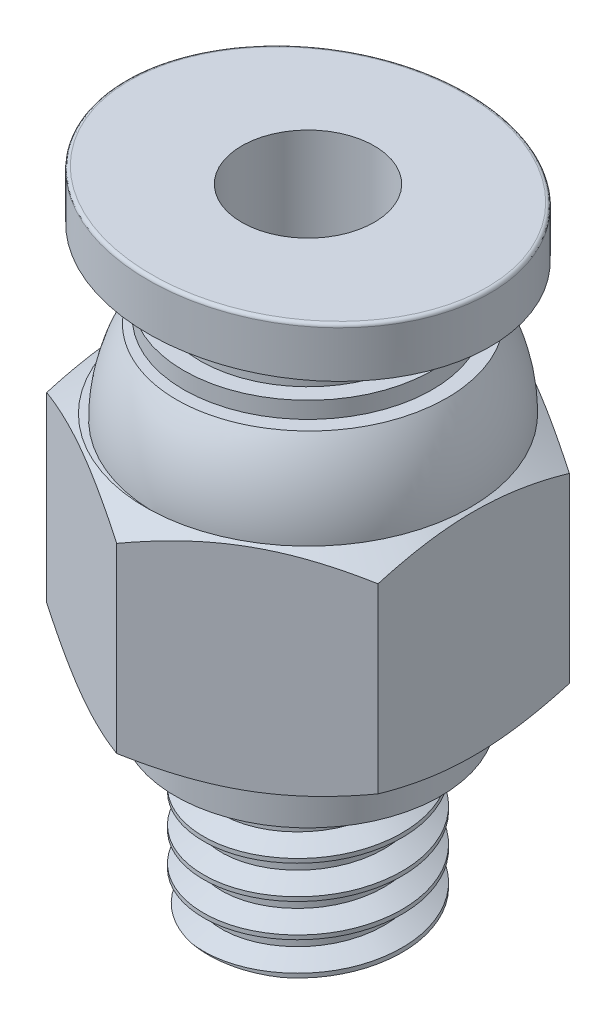
SolidWorks part; units mm, degrees
ref_plane "Спереди" through (0, 0, 0) normal (0, 0, 1) x (1, 0, 0)
ref_plane "Сверху" through (0, 0, 0) normal (0, 1, 0) x (1, 0, 0)
ref_plane "Справа" through (0, 0, 0) normal (1, 0, 0) x (0, 0, -1)
sketch "Эскиз1" plane through (0, 0, 0) normal (0, 1, 0) x (1, 0, 0)
  line L1 (0, 5.7735) -> (-5, 2.8868)
  line L2 (-5, 2.8868) -> (-5, -2.8868)
  line L3 (-5, -2.8868) -> (0, -5.7735)
  line L4 (0, -5.7735) -> (5, -2.8868)
  line L5 (5, -2.8868) -> (5, 2.8868)
  line L6 (5, 2.8868) -> (0, 5.7735)
  circle A0 centre (0, 0) radius 5 construction
  dimension "D1" = 10
extrude "Бобышка-Вытянуть1" add sketch "Эскиз1" along normal mid plane 6.5
sketch "Эскиз4" plane through (0, 0, 0) normal (1, 0, 0) x (0, 0, -1)
  line L0 (-7.1234, 0) -> (0, 0) construction
  line L1 (-4.9, 3.25) -> (-6.9, 2.0953)
  line L2 (-5.7735, 3.25) -> (-2.8868, 3.25) construction
  line L3 (-6.9, 2.0953) -> (-6.9, 3.25)
  line L4 (-6.9, 3.25) -> (-4.9, 3.25)
  line L6 (-6.9, -2.0953) -> (-6.9, -3.25)
  line L7 (-4.9, -3.25) -> (-6.9, -2.0953)
  line L8 (-6.9, -3.25) -> (-4.9, -3.25)
  line L9 (0, 0) -> (0, 4.4661) construction
  dimension "D1" = 2
  dimension "D2" = 4.9
  dimension "D3" = 30
revolve "Вырез-Повернуть1" cut sketch "Эскиз4" angle 360 about L9
sketch "Эскиз5" plane through (0, 3.25, 0) normal (0, 1, 0) x (1, 0, 0)
  line L0 (0.1542, -4.8976) -> (0.1542, 4.8976) construction
  circle A1 centre (0, 0) radius 4.9
  circle A2 centre (0, 0) radius 4.9
  dimension "D1" = 0
revolve "Повернуть2" add sketch "Эскиз5" angle 360 about L0 region at (2.1632, 3.25, 0)
extrude "Вырез-Вытянуть1" cut sketch "Эскиз5<4>" along normal through all from offset 2.5
sketch "Эскиз5<4>" plane through (0, 3.25, 0) normal (0, 1, 0) x (1, 0, 0) same geometry as "Эскиз5"
sketch "Эскиз6" plane through (0, 5.75, 0) normal (0, 1, 0) x (1, 0, 0)
  circle A0 centre (0, 0) radius 3.75
  dimension "D1" = 7.5
extrude "Бобышка-Вытянуть2" add sketch "Эскиз6" along normal blind 0.5
sketch "Эскиз7" plane through (0, -3.25, 0) normal (0, -1, 0) x (1, 0, 0)
  circle A0 centre (0, 0) radius 4
  dimension "D1" = 8
extrude "Бобышка-Вытянуть3" add sketch "Эскиз7" along normal blind 1.5
sketch "Эскиз8" plane through (0, -4.75, 0) normal (0, -1, 0) x (1, 0, 0)
  circle A0 centre (0, 0) radius 3
  dimension "D1" = 6
extrude "Бобышка-Вытянуть4" add sketch "Эскиз8" along normal blind 5
thread "Резьба1" pitch 1 method cut profile "Профиль резьбы1" start angle 0, offset 0, length 10, pitch 1, diameter 6
ref_plane "Плоскость4" through (-3, -4.75, 0) normal (0, 0, 1) x (-1, 0, 0)
sketch "Профиль резьбы1" plane through (-3, -4.75, 0) normal (0, 0, 1) x (-1, 0, 0)
  line L0 (0, 0) -> (0, 1) construction
  line L11 (0, 0) -> (0, 0.875)
  line L12 (0, 0.875) -> (-0.5413, 0.5625)
  line L13 (-0.5413, 0.5625) -> (-0.5413, 0.3125)
  line L15 (-0.5413, 0.3125) -> (0, 0)
  line L17 (-0.5413, 0.4375) -> (0, 0.4375) construction
  point P2 (0, 0)
  dimension "Pitch" = 1
  dimension "Profile_Angle" = 60
  dimension "Profile_Land" = 0.25
  dimension "Profile_Height" = 0.5413
sketch "Эскиз12" plane through (0, 0, 0) normal (1, 0, 0) x (0, 0, -1)
  line L0 (2.4, -9.75) -> (3.4176, -9.1625)
  line L1 (0.9409, -9.75) -> (2.7961, -9.75) construction
  line L2 (3.4176, -9.1625) -> (3.4176, -10.3375)
  line L3 (3.4176, -10.3375) -> (2.4, -9.75)
  line L4 (0, 0) -> (0, -10.9686) construction
  dimension "D1" = 2.4
  dimension "D2" = 3.4176
revolve "Вырез-Повернуть2" cut sketch "Эскиз12" angle 360 about L4
sketch "Эскиз13" plane through (0, -9.75, 0) normal (0, -1, 0) x (1, 0, 0)
  circle A0 centre (0, 0) radius 2
  dimension "D1" = 4
extrude "Вырез-Вытянуть2" cut sketch "Эскиз13" against normal blind 8.5
sketch "Эскиз14" plane through (0, 6.25, 0) normal (0, 1, 0) x (1, 0, 0)
  circle A2 centre (0, 0) radius 3.25
  circle A3 centre (0, 0) radius 3.25
  dimension "D1" = 0.5
extrude "Вырез-Вытянуть3" cut sketch "Эскиз14" against normal blind 7
sketch "Эскиз15" plane through (0, -0.75, 0) normal (0, 1, 0) x (1, 0, 0)
  circle A0 centre (0, 0) radius 1.25
  dimension "D1" = 2.5
extrude "Вырез-Вытянуть4" cut sketch "Эскиз15" against normal blind 7
chamfer "Фаска1" distance 2 angle 45 1 edges at (0, -0.75, 3.25)
chamfer "Фаска2" distance 0.75 angle 45 1 edges at (0, -1.25, -2)
sketch "Эскиз16" plane through (0, 6.25, 0) normal (0, 1, 0) x (1, 0, 0)
  circle A0 centre (0, 0) radius 2.75
  dimension "D1" = 5.5
extrude "Бобышка-Вытянуть5" add sketch "Эскиз16" along normal blind 3 and the other way blind 3 separate body
sketch "Эскиз17" plane through (0, 9.25, 0) normal (0, 1, 0) x (1, 0, 0)
  ellipse E0 centre (0, 0) end of major axis (-5.5, 0) minor radius 4.825
  dimension "D1" = 11
  dimension "D2" = 9.65
extrude "Бобышка-Вытянуть6" add sketch "Эскиз17" against normal blind 1.5
sketch "Эскиз18" plane through (0, 9.25, 0) normal (0, 1, 0) x (1, 0, 0)
  circle A0 centre (0, 0) radius 2
  dimension "D1" = 4
extrude "Вырез-Вытянуть5" cut sketch "Эскиз18" against normal up to next (6 mm away)
fillet "Скругление1" radius 0.1 1 edges at (-5.5, 9.25, 0)
